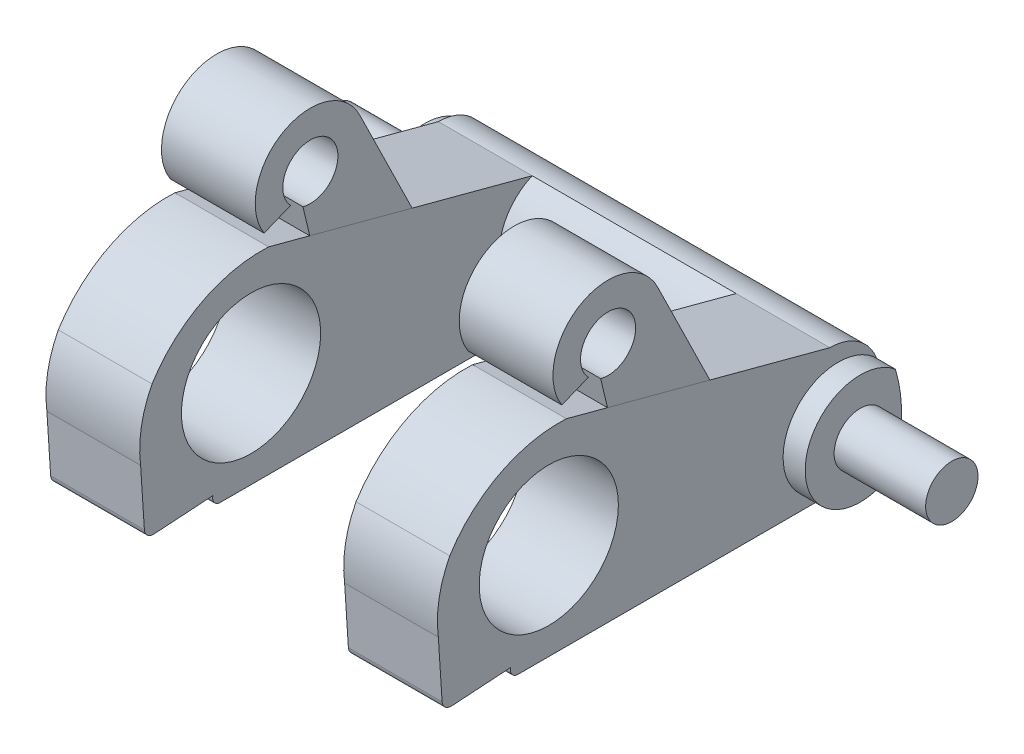
SolidWorks part; units mm, degrees
note: The reader was unsure of these and kept them because the rebuilt part matched: shared geometry of "草图5<6>".
ref_plane "前视基准面" through (0, 0, 0) normal (0, 0, 1) x (1, 0, 0)
ref_plane "上视基准面" through (0, 0, 0) normal (0, 1, 0) x (1, 0, 0)
ref_plane "右视基准面" through (0, 0, 0) normal (1, 0, 0) x (0, 0, -1)
sketch "草图3" plane through (0, 0, 0) normal (0, 1, 0) x (1, 0, 0)
  line L1 (-7.1, 9.25) -> (7.1, 9.25)
  line L2 (-7.1, 9.25) -> (-7.1, -9.25)
  line L3 (-7.1, -9.25) -> (7.1, -9.25)
  line L4 (7.1, 9.25) -> (7.1, -9.25)
  line L5 (-7.1, 9.25) -> (7.1, -9.25) construction
  line L6 (-7.1, -9.25) -> (7.1, 9.25) construction
  point P0 (0, 0)
  dimension "D1" = 14.2
  dimension "D2" = 18.5
extrude "凸台-拉伸1" add sketch "草图3" along normal blind 10
sketch "草图5" plane through (7.1, 0, 0) normal (1, 0, 0) x (0, 0, -1)
  line L0 (-9.25, 0) -> (-9.25, 2)
  line L2 (-9.25, 2) -> (-6.3366, 2) construction
  line L4 (0, 7.5) -> (0.5904, 6.4329) construction
  line L5 (0.5904, 6.4329) -> (7.449, 4.6064) construction
  line L6 (9.25, 2.8054) -> (9.25, 0)
  line L7 (-9.25, 0) -> (9.25, 0)
  line L8 (-9.25, 2) -> (-9.25, 10)
  line L9 (-9.25, 10) -> (9.25, 10)
  line L10 (9.25, 10) -> (9.25, 2.8054)
  line L11 (-0.35, 2) -> (9.25, 2) construction
  line L12 (-5.4333, 0) -> (-9.25, 0)
  line L14 (0.5904, 6.4329) -> (-2.1119, 7.1525)
  line L15 (7.449, 4.6064) -> (0.5904, 6.4329) construction
  line L16 (0.5904, 6.4329) -> (7.449, 4.6064)
  arc A3 (9.25, 2.8054) -> (7.449, 4.6064) centre (7.449, 2.8054) ccw
  circle A4 centre (-2.75, 3.5) radius 2.525
  circle A5 centre (7.75, 2) radius 0.95
  arc A6 (-2.1119, 7.1525) -> (-6.3366, 0) centre (-2.3754, 2.4842) ccw
  arc A7 (-2.1119, 7.1525) -> (0, 7.5) centre (0, 0.9091) cw construction
  point P3 (-2.75, 0.975)
  dimension "D1" = 14.6833
  dimension "D2" = 5.05
  dimension "D3" = 3.5
  dimension "D4" = 6.5
extrude "切除-拉伸3" cut sketch "草图5" against normal through all
extrude "凸台-拉伸2" add sketch "草图5<6>" along normal blind 4.12 contours A5
sketch "草图5<6>" plane through (7.1, 0, 0) normal (1, 0, 0) x (0, 0, -1) same geometry as "草图5"
mirror "镜向1" about plane through (0, 0, 0) normal (1, 0, 0) of "凸台-拉伸2"
sketch "草图17" plane through (7.1, 0, 0) normal (1, 0, 0) x (0, 0, -1)
  line L1 (7.449, 4.6064) -> (-2.1119, 7.1525) construction
  line L3 (-0.6203, 6.7553) -> (0.0926, 6.5654)
  line L5 (-0.8676, 7.792) -> (-0.6203, 6.7553)
  line L7 (-1.3137, 8.056) -> (-2.2764, 7.6664)
  line L8 (3.0934, 5.7663) -> (1.1972, 9.6353)
  line L9 (7.449, 4.6064) -> (-2.1119, 7.1525) construction
  line L10 (3.0934, 5.7663) -> (0.0926, 6.5654)
  arc A0 (1.1972, 9.6353) -> (-2.2764, 7.6664) centre (-0.5987, 8.7551) ccw
  arc A1 (-0.8676, 7.792) -> (-1.3137, 8.056) centre (-0.5987, 8.7551) ccw
  point P7 (-0.6203, 6.7553)
  dimension "D1" = 2
  dimension "D2" = 1
extrude "凸台-拉伸3" add sketch "草图17" against normal blind 14.2 separate body
sketch "草图14" plane through (0, 0, 0) normal (0, -1, 0) x (1, 0, 0)
  line L24 (7.1, -9.25) -> (-7.1, -9.25) construction
  line L25 (-3.7, -6.25) -> (3.7, -6.25)
  line L26 (-3.7, -6.25) -> (-3.7, 8.9537)
  line L27 (-3.7, 8.9537) -> (3.7, 8.9537)
  line L28 (3.7, -6.25) -> (3.7, 8.9537)
  line L29 (-7.1, 5.275) -> (-7.1, 0.225) construction
  line L30 (7.1, 6.3366) -> (7.1, -9.25) construction
  dimension "D1" = 3
  dimension "D2" = 3.4
  dimension "D3" = 3.4
extrude "切除-拉伸6" cut sketch "草图14" against normal through all both and the other way through all contours L26 L27 L28 L25
sketch "草图20" plane through (7.1, 0, 0) normal (1, 0, 0) x (0, 0, -1)
  line L1 (-6.3366, 0) -> (9.25, 0) construction
  arc A9 (9.0261, 3.54) -> (9.0261, 0.46) centre (7.75, 2) ccw
  arc A10 (9.0261, 3.54) -> (9.0261, 0.46) centre (3.8413, 2) cw
  point P9 (7.449, 4.6064)
  point P10 (9.25, 2.8054)
  point P12 (9.25, 0)
  point P19 (6.3117, 0)
  point P22 (9.25, 0)
extrude "凸台-拉伸4" add sketch "草图20" along normal blind 0.8
mirror "镜向2" about plane through (0, 0, 0) normal (1, 0, 0) of "凸台-拉伸4"
fillet "圆角1" radius 2 1 edges at (0, 4.9257, -6.25)
sketch "草图23" plane through (-7.1, 0, 0) normal (-1, 0, 0) x (0, 0, 1)
  line L1 (-7.75, 0) -> (6.3366, 0) construction
  line L6 (4.1333, 0) -> (3.8808, 0)
  line L11 (4.1333, 0.35) -> (6.9981, 0.1633)
  line L12 (4.1333, 0) -> (6.9981, 0)
  line L13 (6.9981, 0) -> (6.9981, 0.1633)
  arc A0 (4.1333, 0.35) -> (3.8808, 0) centre (3.8658, 0.2769) cw
  dimension "D1" = 0.35
sketch "草图28" plane through (-7.1, 0, 0) normal (-1, 0, 0) x (0, 0, 1)
  line L0 (4.1333, 0.35) -> (6.9981, 0.1633)
  line L1 (6.9981, 0.1633) -> (6.9981, 0)
  line L2 (6.9981, 0) -> (3.8808, 0)
  arc A0 (4.1333, 0.35) -> (3.8808, 0) centre (3.8658, 0.2769) cw
extrude "切除-拉伸16" cut sketch "草图28" against normal through all
sketch "草图31" plane through (0, 6.1537, -1.6387) normal (0, -0.9663, 0.2573) x (1, 0, 0)
  line L0 (-3.7, 3.7501) -> (-3.7, -6.0395) construction
  line L1 (-3.7, -1.5054) -> (3.7, -1.5054)
  line L2 (-3.7, -1.5054) -> (-3.7, 9.1171)
  line L3 (-3.7, 9.1171) -> (3.7, 9.1171)
  line L4 (3.7, -1.5054) -> (3.7, 9.1171)
  line L5 (-7.1, -1.5054) -> (7.1, -1.5054) construction
extrude "切除-拉伸17" cut sketch "草图31" against normal through all
sketch "草图33" plane through (7.1, 0, 0) normal (1, 0, 0) x (0, 0, -1)
  line L1 (-4.1333, 0.35) -> (-6.9981, 0.1633) construction
  line L4 (-6.3413, 4.9609) -> (-7.6809, 4.9609)
  line L5 (-7.6809, 4.9609) -> (-7.6809, 0)
  line L6 (-7.6809, 0) -> (-5.5657, 0.2566)
  arc A1 (-5.5657, 0.2566) -> (-6.3413, 4.9609) centre (-2.8114, 3.1268) cw
  arc A2 (-2.1119, 7.1525) -> (-6.4545, 0.1987) centre (-2.3754, 2.4842) ccw construction
extrude "切除-拉伸19" cut sketch "草图33" against normal through all
sketch "草图35" plane through (-7.1, 0, 0) normal (-1, 0, 0) x (0, 0, 1)
  line L2 (6.5979, 0.1894) -> (5.5657, 0.2566)
  line L3 (5.5657, 0.2566) -> (6.7893, 3.1268)
  line L4 (6.7893, 3.1268) -> (6.5979, 0.1894)
  arc A0 (5.5657, 0.2566) -> (6.3413, 4.9609) centre (2.8114, 3.1268) ccw construction
extrude "凸台-拉伸7" add sketch "草图35" against normal blind 14.2
sketch "草图36" plane through (0, 0.6168, 0.0402) normal (0, -0.9979, -0.065) x (1, 0, 0)
  line L1 (-3.7, 5.5373) -> (3.7, 5.5373)
  line L2 (-3.7, 5.5373) -> (-3.7, 8.2259)
  line L3 (-3.7, 8.2259) -> (3.7, 8.2259)
  line L4 (3.7, 5.5373) -> (3.7, 8.2259)
extrude "切除-拉伸20" cut sketch "草图36" against normal through all
sketch "草图38" plane through (-7.1, 0, 0) normal (-1, 0, 0) x (0, 0, 1)
  line L0 (4.1333, 0.35) -> (6.9981, 0.1633) construction
  line L1 (6.5979, 0.1894) -> (6.7557, 2.6105) construction
  line L3 (6.5979, 0.1894) -> (6.2733, 0.2105)
  line L4 (6.62, 0.5285) -> (6.6798, 0.184)
  line L5 (6.6798, 0.184) -> (6.5979, 0.1894)
  arc A0 (6.2733, 0.2105) -> (6.62, 0.5285) centre (6.2877, 0.5428) ccw
extrude "切除-拉伸21" cut sketch "草图38" against normal through all
